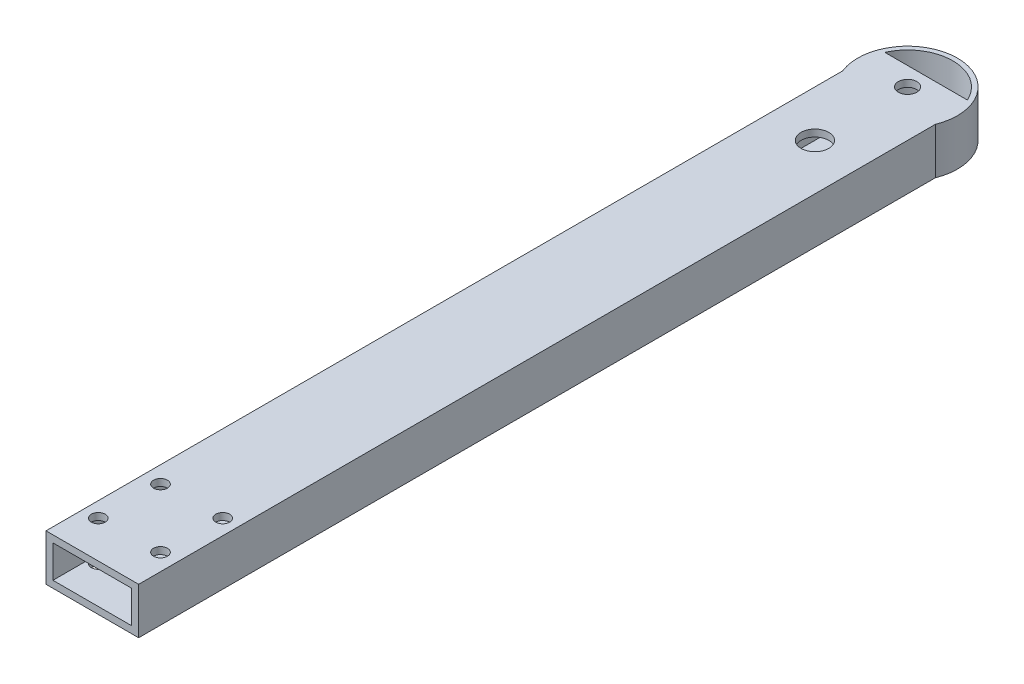
SolidWorks part; units mm, degrees
ref_plane "Front Plane" through (0, 0, 0) normal (0, 0, 1) x (1, 0, 0)
ref_plane "Top Plane" through (0, 0, 0) normal (0, 1, 0) x (1, 0, 0)
ref_plane "Right Plane" through (0, 0, 0) normal (1, 0, 0) x (0, 0, -1)
sketch "Sketch1" plane through (0, 0, 0) normal (0, 0, 1) x (1, 0, 0)
  line L0 (8.5, -3.5) -> (-8.5, -3.5)
  line L1 (10, -5) -> (-10, -5)
  line L2 (10, -5) -> (10, 5)
  line L3 (10, 5) -> (-10, 5)
  line L4 (-10, -5) -> (-10, 5)
  line L5 (10, -5) -> (-10, 5) construction
  line L6 (10, 5) -> (-10, -5) construction
  line L7 (-8.5, -3.5) -> (-8.5, 3.5)
  line L8 (8.5, 3.5) -> (-8.5, 3.5)
  line L9 (8.5, -3.5) -> (8.5, 3.5)
  point P0 (0, 0)
  dimension "D1" = 20
  dimension "D2" = 10
  dimension "D3" = 1.5
extrude "Boss-Extrude1" add sketch "Sketch1" along normal blind 180
sketch "Sketch2" plane through (0, 5, 0) normal (0, 1, 0) x (1, 0, 0)
  line L0 (0, -180) -> (0, -154.1805) construction
  line L1 (10, -180) -> (-10, -180) construction
  line L2 (6.364, -171.6464) -> (-6.364, -158.9185) construction
  line L3 (-6.7175, -172) -> (6.7175, -158.565) construction
  circle A0 centre (6.364, -171.6464) radius 1.5
  circle A1 centre (-6.7175, -172) radius 1.5
  circle A2 centre (6.7175, -158.565) radius 1.5
  circle A3 centre (-6.364, -158.9185) radius 1.5
  point P13 (0, -165.2825)
  point P14 (0, -165.2825)
  dimension "D1" = 3
  dimension "D2" = 19
  dimension "D3" = 18
  dimension "D4" = 8
  dimension "D5" = 14.7175
extrude "Cut-Extrude1" cut sketch "Sketch2" against normal through all
sketch "Sketch3" plane through (0, 5, 0) normal (0, 1, 0) x (1, 0, 0)
  line L0 (0, -188.574) -> (0, -5.39) construction
  line L1 (-6.364, -158.9185) -> (6.364, -171.6464) construction
  line L2 (10, 0) -> (-10, 0) construction
  circle A0 centre (0, -4) radius 2
  circle A1 centre (0, -24) radius 3
  point P11 (0, -165.2825)
  dimension "D1" = 6
  dimension "D2" = 4
  dimension "D3" = 20
  dimension "D4" = 4
  dimension "D5" = 161.2825
extrude "Cut-Extrude2" cut sketch "Sketch3" against normal through all
sketch "Sketch4" plane through (0, 5, 0) normal (0, 1, 0) x (1, 0, 0)
  line L0 (0, 0) -> (0, -180) construction
  line L3 (10, -180) -> (-10, -180) construction
  point P2 (0, -4)
sketch "Sketch5" plane through (0, 5, 0) normal (0, 1, 0) x (1, 0, 0)
  circle A0 centre (0, -4) radius 10.7703
  circle A1 centre (0, -4) radius 9.7703
  dimension "D1" = 1
extrude "Boss-Extrude2" add sketch "Sketch5" against normal blind 10
ref_axis "Axis1" through (0, 3.5, 4) along (0, 1, 0)
